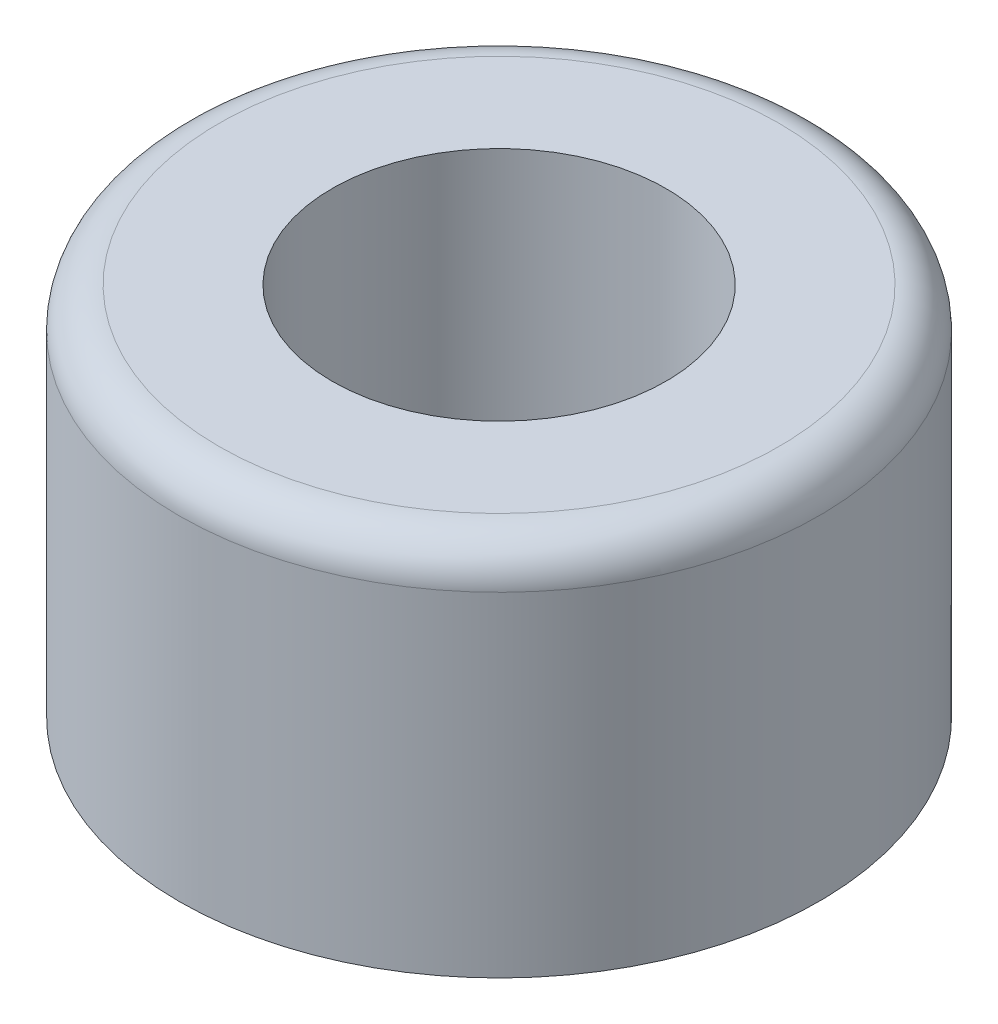
SolidWorks part; units mm, degrees
material "ABS PC"
ref_plane "Front Plane" through (0, 0, 0) normal (0, 0, 1) x (1, 0, 0)
ref_plane "Top Plane" through (0, 0, 0) normal (0, 1, 0) x (1, 0, 0)
ref_plane "Right Plane" through (0, 0, 0) normal (1, 0, 0) x (0, 0, -1)
sketch "Sketch1" plane through (0, 0, 0) normal (0, 1, 0) x (1, 0, 0)
  circle A0 centre (0, 0) radius 4.064
  circle A1 centre (0, 0) radius 2.1209
  dimension "D1" = 8.128
  dimension "D2" = 4.2418
extrude "Extrude1" add sketch "Sketch1" along normal mid plane 4.7498
fillet "Fillet1" radius 0.508 1 edges at (0, 2.3749, 4.064)
ref_axis "Axis1" through (0, -3.1636, 0) along (0, 1, 0)
